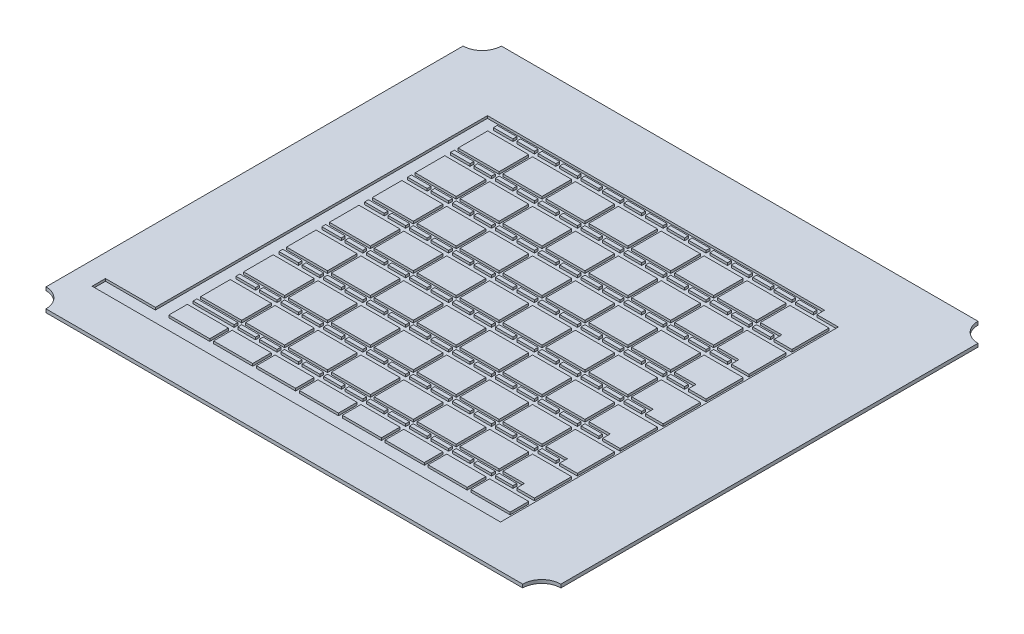
SolidWorks part; units mm, degrees
material "Acrylic (Medium-high impact)"
ref_plane "Front Plane" through (0, 0, 0) normal (0, 0, 1) x (1, 0, 0)
ref_plane "Top Plane" through (0, 0, 0) normal (0, 1, 0) x (1, 0, 0)
ref_plane "Right Plane" through (0, 0, 0) normal (1, 0, 0) x (0, 0, -1)
sketch "Sketch1" plane through (0, 0, 0) normal (0, 1, 0) x (1, 0, 0)
  line L1 (-342.9, -303.2125) -> (342.9, -303.2125)
  line L2 (-342.9, -303.2125) -> (-342.9, 303.2125)
  line L3 (-342.9, 303.2125) -> (342.9, 303.2125)
  line L4 (342.9, -303.2125) -> (342.9, 303.2125)
  line L5 (-342.9, -303.2125) -> (342.9, 303.2125) construction
  line L6 (-342.9, 303.2125) -> (342.9, -303.2125) construction
  point P0 (0, 0)
  dimension "D1" = 685.8
  dimension "D2" = 606.425
extrude "Boss-Extrude1" add sketch "Sketch1" along normal blind 4.4958
sketch "Sketch2" plane through (0, 4.4958, 0) normal (0, 1, 0) x (1, 0, 0)
  line L0 (0, 0) -> (0, 228.6) construction
  line L1 (0, 228.6) -> (228.6, 228.6) construction
  line L2 (228.6, 228.6) -> (228.6, -228.6) construction
  line L3 (228.6, -228.6) -> (-228.6, -228.6) construction
  line L4 (-228.6, -228.6) -> (-228.6, 228.6) construction
  line L5 (-228.6, 228.6) -> (0, 228.6) construction
  line L6 (0, 0) -> (0, -228.6) construction
  line L7 (-57.15, -228.6) -> (-57.15, 228.6) construction
  line L8 (-114.3, 228.6) -> (-114.3, -228.6) construction
  line L9 (-228.6, 0) -> (228.6, 0) construction
  line L10 (114.3, 228.6) -> (114.3, -228.6) construction
  line L11 (57.15, 228.6) -> (57.15, -228.6) construction
  line L12 (-228.6, 171.45) -> (228.6, 171.45) construction
  line L13 (-228.6, 114.3) -> (228.6, 114.3) construction
  line L14 (-228.6, 57.15) -> (228.6, 57.15) construction
  line L15 (228.6, -57.15) -> (-228.6, -57.15) construction
  line L16 (-228.6, -114.3) -> (228.6, -114.3) construction
  line L17 (228.6, -171.45) -> (-228.6, -171.45) construction
  line L18 (-171.45, 228.6) -> (-171.45, -228.6) construction
  line L19 (171.45, 228.6) -> (171.45, -228.6) construction
  dimension "D1" = 228.6
  dimension "D2" = 457.2
  dimension "D3" = 228.6
  dimension "D4" = 228.6
  dimension "D5" = 57.15
  dimension "D6" = 57.15
  dimension "D7" = 57.15
  dimension "D8" = 57.15
  dimension "D9" = 57.15
  dimension "D10" = 57.15
  dimension "D11" = 57.15
  dimension "D12" = 57.15
  dimension "D13" = 57.15
  dimension "D14" = 57.15
  dimension "D15" = 57.15
sketch "Sketch3" plane through (0, 4.4958, 0) normal (0, 1, 0) x (1, 0, 0)
  line L0 (0, 0) -> (0, -228.6) construction
  line L5 (-246.4078, -228.6) -> (-312.907, -228.6)
  line L6 (226.06, -228.6) -> (173.99, -228.6)
  line L7 (-228.6, -203.835) -> (-228.6, -228.6)
  line L8 (-228.6, 0) -> (228.6, 0) construction
  line L9 (-228.6, -191.135) -> (-228.6, -196.215)
  line L14 (231.14, -228.8655) -> (231.14, -246.38)
  line L15 (231.14, -246.38) -> (-312.907, -246.38)
  line L20 (-312.907, -228.6) -> (-312.907, -246.38)
  line L27 (-228.6, 208.915) -> (-228.6, 203.835)
  line L34 (-246.4078, 213.7295) -> (-246.4078, -228.6)
  line L39 (-228.6, -146.685) -> (-228.6, -186.055)
  line L40 (-228.6, -133.985) -> (-228.6, -139.065)
  line L43 (-228.6, -89.535) -> (-228.6, -128.905)
  line L45 (-228.6, -76.835) -> (-228.6, -81.915)
  line L46 (-228.6, -19.685) -> (-228.6, -24.765)
  line L51 (-228.6, -32.385) -> (-228.6, -71.755)
  line L52 (-228.6, 37.465) -> (-228.6, 32.385)
  line L57 (-228.6, 24.765) -> (-228.6, -14.605)
  line L58 (-228.6, 81.915) -> (-228.6, 42.545)
  line L68 (-228.6, 94.615) -> (-228.6, 89.535)
  line L71 (-228.6, 139.065) -> (-228.6, 99.695)
  line L73 (-228.6, 151.765) -> (-228.6, 146.685)
  line L74 (-228.6, 196.215) -> (-228.6, 156.845)
  line L90 (-173.99, -228.6) -> (-228.6, -228.6)
  line L94 (-116.84, -228.6) -> (-168.91, -228.6)
  line L127 (-59.69, -228.6) -> (-111.76, -228.6)
  line L130 (-2.54, -228.6) -> (-54.61, -228.6)
  line L159 (54.61, -228.6) -> (2.54, -228.6)
  line L162 (111.76, -228.6) -> (59.69, -228.6)
  line L166 (168.91, -228.6) -> (116.84, -228.6)
  line L171 (-168.91, 213.7295) -> (-246.4078, 213.7295)
  line L807 (202.565, -76.835) -> (202.565, -71.755)
  line L808 (226.06, -76.835) -> (226.06, -72.2386)
  line L809 (226.06, -133.985) -> (226.06, -128.905)
  line L810 (202.565, -133.985) -> (202.565, -128.905)
  line L811 (202.565, -191.135) -> (202.565, -186.055)
  line L812 (226.06, -191.135) -> (226.06, -186.055)
  line L813 (197.485, 32.385) -> (173.99, 32.385)
  line L814 (226.06, 37.465) -> (226.06, 42.545)
  line L815 (202.565, 37.465) -> (202.565, 42.545)
  line L816 (202.565, -19.685) -> (202.565, -14.605)
  line L817 (226.06, -19.685) -> (226.06, -14.605)
  line L818 (226.06, -71.755) -> (226.06, -72.2386)
  line L819 (197.485, -196.215) -> (173.99, -196.215)
  line L820 (197.485, 89.535) -> (173.99, 89.535)
  line L821 (197.485, 94.615) -> (173.99, 94.615)
  line L822 (197.485, 146.685) -> (173.99, 146.685)
  line L823 (197.485, 151.765) -> (173.99, 151.765)
  line L824 (83.185, 203.835) -> (59.69, 203.835)
  line L825 (83.185, 208.915) -> (59.69, 208.915)
  line L826 (140.335, 203.835) -> (116.84, 203.835)
  line L827 (140.335, 208.915) -> (116.84, 208.915)
  line L828 (197.485, 203.835) -> (173.99, 203.835)
  line L829 (197.485, 208.915) -> (173.99, 208.915)
  line L830 (140.335, 32.385) -> (116.84, 32.385)
  line L831 (140.335, 37.465) -> (116.84, 37.465)
  line L832 (140.335, 89.535) -> (116.84, 89.535)
  line L833 (140.335, 94.615) -> (116.84, 94.615)
  line L834 (140.335, 146.685) -> (116.84, 146.685)
  line L835 (140.335, 151.765) -> (116.84, 151.765)
  line L836 (83.185, 146.685) -> (59.69, 146.685)
  line L837 (83.185, 151.765) -> (59.69, 151.765)
  line L838 (83.185, 89.535) -> (59.69, 89.535)
  line L839 (83.185, 94.615) -> (59.69, 94.615)
  line L840 (83.185, 32.385) -> (59.69, 32.385)
  line L841 (83.185, 37.465) -> (59.69, 37.465)
  line L842 (26.035, 32.385) -> (2.54, 32.385)
  line L843 (26.035, 37.465) -> (2.54, 37.465)
  line L844 (26.035, 89.535) -> (2.54, 89.535)
  line L845 (26.035, 94.615) -> (2.54, 94.615)
  line L846 (26.035, 146.685) -> (2.54, 146.685)
  line L847 (26.035, 151.765) -> (2.54, 151.765)
  line L848 (26.035, 203.835) -> (2.54, 203.835)
  line L849 (26.035, 208.915) -> (2.54, 208.915)
  line L850 (-31.115, 32.385) -> (-54.61, 32.385)
  line L851 (-31.115, 37.465) -> (-54.61, 37.465)
  line L852 (-31.115, 89.535) -> (-54.61, 89.535)
  line L853 (-31.115, 94.615) -> (-54.61, 94.615)
  line L854 (-202.565, 89.535) -> (-228.6, 89.535)
  line L855 (-202.565, 94.615) -> (-228.6, 94.615)
  line L856 (-202.565, 32.385) -> (-228.6, 32.385)
  line L857 (-202.565, 37.465) -> (-228.6, 37.465)
  line L858 (-145.415, 37.465) -> (-168.91, 37.465)
  line L859 (-145.415, 32.385) -> (-168.91, 32.385)
  line L860 (-88.265, 32.385) -> (-111.76, 32.385)
  line L861 (-88.265, 37.465) -> (-111.76, 37.465)
  line L862 (-88.265, 89.535) -> (-111.76, 89.535)
  line L863 (-88.265, 94.615) -> (-111.76, 94.615)
  line L864 (-145.415, 89.535) -> (-168.91, 89.535)
  line L865 (-145.415, 94.615) -> (-168.91, 94.615)
  line L866 (-88.265, 146.685) -> (-111.76, 146.685)
  line L867 (-88.265, 151.765) -> (-111.76, 151.765)
  line L868 (-31.115, 146.685) -> (-54.61, 146.685)
  line L869 (-31.115, 151.765) -> (-54.61, 151.765)
  line L870 (-31.115, 203.835) -> (-54.61, 203.835)
  line L871 (-31.115, 208.915) -> (-54.61, 208.915)
  line L872 (-88.265, 203.835) -> (-111.76, 203.835)
  line L873 (-88.265, 208.915) -> (-111.76, 208.915)
  line L874 (-145.415, 203.835) -> (-168.91, 203.835)
  line L875 (-145.415, 208.915) -> (-168.91, 208.915)
  line L876 (-145.415, 146.685) -> (-168.91, 146.685)
  line L877 (-145.415, 151.765) -> (-168.91, 151.765)
  line L878 (-202.565, 146.685) -> (-228.6, 146.685)
  line L879 (-202.565, 151.765) -> (-228.6, 151.765)
  line L880 (-202.565, 203.835) -> (-228.6, 203.835)
  line L881 (-202.565, 208.915) -> (-228.6, 208.915)
  line L882 (197.485, -139.065) -> (173.99, -139.065)
  line L883 (197.485, -133.985) -> (173.99, -133.985)
  line L884 (197.485, -191.135) -> (173.99, -191.135)
  line L885 (140.335, -196.215) -> (116.84, -196.215)
  line L886 (140.335, -191.135) -> (116.84, -191.135)
  line L887 (140.335, -139.065) -> (116.84, -139.065)
  line L888 (140.335, -133.985) -> (116.84, -133.985)
  line L889 (83.185, -139.065) -> (59.69, -139.065)
  line L890 (83.185, -133.985) -> (59.69, -133.985)
  line L891 (83.185, -196.215) -> (59.69, -196.215)
  line L892 (83.185, -191.135) -> (59.69, -191.135)
  line L893 (26.035, -196.215) -> (2.54, -196.215)
  line L894 (26.035, -191.135) -> (2.54, -191.135)
  line L895 (26.035, -139.065) -> (2.54, -139.065)
  line L896 (26.035, -133.985) -> (2.54, -133.985)
  line L897 (-31.115, -139.065) -> (-54.61, -139.065)
  line L898 (-31.115, -133.985) -> (-54.61, -133.985)
  line L899 (-31.115, -196.215) -> (-54.61, -196.215)
  line L900 (-31.115, -191.135) -> (-54.61, -191.135)
  line L901 (-88.265, -196.215) -> (-111.76, -196.215)
  line L902 (-88.265, -191.135) -> (-111.76, -191.135)
  line L903 (-145.415, -196.215) -> (-168.91, -196.215)
  line L904 (-145.415, -191.135) -> (-168.91, -191.135)
  line L905 (-88.265, -139.065) -> (-111.76, -139.065)
  line L906 (-88.265, -133.985) -> (-111.76, -133.985)
  line L907 (-145.415, -139.065) -> (-168.91, -139.065)
  line L908 (-145.415, -133.985) -> (-168.91, -133.985)
  line L909 (-202.565, -139.065) -> (-228.6, -139.065)
  line L910 (-202.565, -133.985) -> (-228.6, -133.985)
  line L911 (-145.415, -81.915) -> (-168.91, -81.915)
  line L912 (-145.415, -76.835) -> (-168.91, -76.835)
  line L913 (-202.565, -81.915) -> (-228.6, -81.915)
  line L914 (-202.565, -76.835) -> (-228.6, -76.835)
  line L915 (-88.265, -81.915) -> (-111.76, -81.915)
  line L916 (-88.265, -76.835) -> (-111.76, -76.835)
  line L917 (-31.115, -81.915) -> (-54.61, -81.915)
  line L918 (-31.115, -76.835) -> (-54.61, -76.835)
  line L919 (26.035, -81.915) -> (2.54, -81.915)
  line L920 (26.035, -76.835) -> (2.54, -76.835)
  line L921 (83.185, -81.915) -> (59.69, -81.915)
  line L922 (83.185, -76.835) -> (59.69, -76.835)
  line L923 (140.335, -81.915) -> (116.84, -81.915)
  line L924 (140.335, -76.835) -> (116.84, -76.835)
  line L925 (197.485, -81.915) -> (173.99, -81.915)
  line L926 (197.485, -76.835) -> (173.99, -76.835)
  line L927 (197.485, -196.215) -> (197.485, -191.135)
  line L928 (202.565, -196.215) -> (202.565, -191.135)
  line L929 (140.335, -196.215) -> (140.335, -191.135)
  line L930 (145.415, -196.215) -> (145.415, -191.135)
  line L931 (83.185, -196.215) -> (83.185, -191.135)
  line L932 (88.265, -196.215) -> (88.265, -191.135)
  line L933 (26.035, -196.215) -> (26.035, -191.135)
  line L934 (31.115, -196.215) -> (31.115, -191.135)
  line L935 (-31.115, -196.215) -> (-31.115, -191.135)
  line L936 (-26.035, -196.215) -> (-26.035, -191.135)
  line L937 (-83.185, -196.215) -> (-83.185, -191.135)
  line L938 (-88.265, -196.215) -> (-88.265, -191.135)
  line L939 (-140.335, -196.215) -> (-140.335, -191.135)
  line L940 (-145.415, -196.215) -> (-145.415, -191.135)
  line L941 (-197.485, -196.215) -> (-197.485, -191.135)
  line L942 (-202.565, -196.215) -> (-202.565, -191.135)
  line L943 (197.485, -139.065) -> (197.485, -133.985)
  line L944 (202.565, -139.065) -> (202.565, -133.985)
  line L945 (140.335, -139.065) -> (140.335, -133.985)
  line L946 (145.415, -139.065) -> (145.415, -133.985)
  line L947 (83.185, -139.065) -> (83.185, -133.985)
  line L948 (88.265, -139.065) -> (88.265, -133.985)
  line L949 (26.035, -139.065) -> (26.035, -133.985)
  line L950 (31.115, -139.065) -> (31.115, -133.985)
  line L951 (-31.115, -139.065) -> (-31.115, -133.985)
  line L952 (-26.035, -139.065) -> (-26.035, -133.985)
  line L953 (-83.185, -139.065) -> (-83.185, -133.985)
  line L954 (-88.265, -139.065) -> (-88.265, -133.985)
  line L955 (-140.335, -139.065) -> (-140.335, -133.985)
  line L956 (-145.415, -139.065) -> (-145.415, -133.985)
  line L957 (-197.485, -139.065) -> (-197.485, -133.985)
  line L958 (-202.565, -139.065) -> (-202.565, -133.985)
  line L959 (197.485, -81.915) -> (197.485, -76.835)
  line L960 (202.565, -81.915) -> (202.565, -76.835)
  line L961 (140.335, -81.915) -> (140.335, -76.835)
  line L962 (145.415, -81.915) -> (145.415, -76.835)
  line L963 (83.185, -81.915) -> (83.185, -76.835)
  line L964 (88.265, -81.915) -> (88.265, -76.835)
  line L965 (26.035, -81.915) -> (26.035, -76.835)
  line L966 (31.115, -81.915) -> (31.115, -76.835)
  line L967 (-31.115, -81.915) -> (-31.115, -76.835)
  line L968 (-26.035, -81.915) -> (-26.035, -76.835)
  line L969 (-83.185, -81.915) -> (-83.185, -76.835)
  line L970 (-88.265, -81.915) -> (-88.265, -76.835)
  line L971 (-140.335, -81.915) -> (-140.335, -76.835)
  line L972 (-145.415, -81.915) -> (-145.415, -76.835)
  line L973 (-197.485, -81.915) -> (-197.485, -76.835)
  line L974 (-202.565, -81.915) -> (-202.565, -76.835)
  line L975 (197.485, 203.835) -> (197.485, 208.915)
  line L976 (202.565, 203.5695) -> (202.565, 208.6495)
  line L977 (140.335, 203.835) -> (140.335, 208.915)
  line L978 (145.415, 203.835) -> (145.415, 208.915)
  line L979 (83.185, 203.835) -> (83.185, 208.915)
  line L980 (88.265, 203.835) -> (88.265, 208.915)
  line L981 (26.035, 203.835) -> (26.035, 208.915)
  line L982 (31.115, 203.835) -> (31.115, 208.915)
  line L983 (-31.115, 203.835) -> (-31.115, 208.915)
  line L984 (-26.035, 203.835) -> (-26.035, 208.915)
  line L985 (-83.185, 203.835) -> (-83.185, 208.915)
  line L986 (-88.265, 203.835) -> (-88.265, 208.915)
  line L987 (-140.335, 203.835) -> (-140.335, 208.915)
  line L988 (-145.415, 203.835) -> (-145.415, 208.915)
  line L989 (-197.485, 203.835) -> (-197.485, 208.915)
  line L990 (-202.565, 203.835) -> (-202.565, 208.915)
  line L991 (197.485, 146.685) -> (197.485, 151.765)
  line L992 (202.565, 146.685) -> (202.565, 151.765)
  line L993 (140.335, 146.685) -> (140.335, 151.765)
  line L994 (145.415, 146.685) -> (145.415, 151.765)
  line L995 (83.185, 146.685) -> (83.185, 151.765)
  line L996 (88.265, 146.685) -> (88.265, 151.765)
  line L997 (26.035, 146.685) -> (26.035, 151.765)
  line L998 (31.115, 146.685) -> (31.115, 151.765)
  line L999 (-31.115, 146.685) -> (-31.115, 151.765)
  line L1000 (-26.035, 146.685) -> (-26.035, 151.765)
  line L1001 (-83.185, 146.685) -> (-83.185, 151.765)
  line L1002 (-88.265, 146.685) -> (-88.265, 151.765)
  line L1003 (-140.335, 146.685) -> (-140.335, 151.765)
  line L1004 (-145.415, 146.685) -> (-145.415, 151.765)
  line L1005 (-197.485, 146.685) -> (-197.485, 151.765)
  line L1006 (-202.565, 146.685) -> (-202.565, 151.765)
  line L1007 (197.485, 89.535) -> (197.485, 94.615)
  line L1008 (202.565, 89.535) -> (202.565, 94.615)
  line L1009 (140.335, 89.535) -> (140.335, 94.615)
  line L1010 (145.415, 89.535) -> (145.415, 94.615)
  line L1011 (83.185, 89.535) -> (83.185, 94.615)
  line L1012 (88.265, 89.535) -> (88.265, 94.615)
  line L1013 (26.035, 89.535) -> (26.035, 94.615)
  line L1014 (31.115, 89.535) -> (31.115, 94.615)
  line L1015 (-31.115, 89.535) -> (-31.115, 94.615)
  line L1016 (-26.035, 89.535) -> (-26.035, 94.615)
  line L1017 (-83.185, 89.535) -> (-83.185, 94.615)
  line L1018 (-88.265, 89.535) -> (-88.265, 94.615)
  line L1019 (-140.335, 89.535) -> (-140.335, 94.615)
  line L1020 (-145.415, 89.535) -> (-145.415, 94.615)
  line L1021 (-197.485, 89.535) -> (-197.485, 94.615)
  line L1022 (-202.565, 89.535) -> (-202.565, 94.615)
  line L1023 (197.485, 32.385) -> (197.485, 37.465)
  line L1024 (202.565, 32.385) -> (202.565, 37.465)
  line L1025 (140.335, 32.385) -> (140.335, 37.465)
  line L1026 (145.415, 32.385) -> (145.415, 37.465)
  line L1027 (83.185, 32.385) -> (83.185, 37.465)
  line L1028 (88.265, 32.385) -> (88.265, 37.465)
  line L1029 (26.035, 32.385) -> (26.035, 37.465)
  line L1030 (31.115, 32.385) -> (31.115, 37.465)
  line L1031 (-31.115, 32.385) -> (-31.115, 37.465)
  line L1032 (-26.035, 32.385) -> (-26.035, 37.465)
  line L1033 (-83.185, 32.385) -> (-83.185, 37.465)
  line L1034 (-88.265, 32.385) -> (-88.265, 37.465)
  line L1035 (-140.335, 32.385) -> (-140.335, 37.465)
  line L1036 (-145.415, 32.385) -> (-145.415, 37.465)
  line L1037 (-197.485, 32.385) -> (-197.485, 37.465)
  line L1038 (-202.565, 32.385) -> (-202.565, 37.465)
  line L1039 (-202.565, -24.765) -> (-228.6, -24.765)
  line L1040 (-202.565, -19.685) -> (-228.6, -19.685)
  line L1041 (-145.415, -24.765) -> (-168.91, -24.765)
  line L1042 (-145.415, -19.685) -> (-168.91, -19.685)
  line L1043 (-88.265, -24.765) -> (-111.76, -24.765)
  line L1044 (-88.265, -19.685) -> (-111.76, -19.685)
  line L1045 (-31.115, -24.765) -> (-54.61, -24.765)
  line L1046 (-31.115, -19.685) -> (-54.61, -19.685)
  line L1047 (26.035, -24.765) -> (2.54, -24.765)
  line L1048 (26.035, -19.685) -> (2.54, -19.685)
  line L1049 (83.185, -24.765) -> (59.69, -24.765)
  line L1050 (83.185, -19.685) -> (59.69, -19.685)
  line L1051 (140.335, -24.765) -> (116.84, -24.765)
  line L1052 (140.335, -19.685) -> (116.84, -19.685)
  line L1053 (197.485, -24.765) -> (173.99, -24.765)
  line L1054 (197.485, -19.685) -> (173.99, -19.685)
  line L1055 (-197.485, -24.765) -> (-197.485, -19.685)
  line L1056 (-202.565, -24.765) -> (-202.565, -19.685)
  line L1057 (-140.335, -24.765) -> (-140.335, -19.685)
  line L1058 (-145.415, -24.765) -> (-145.415, -19.685)
  line L1059 (-83.185, -24.765) -> (-83.185, -19.685)
  line L1060 (-88.265, -24.765) -> (-88.265, -19.685)
  line L1061 (-26.035, -24.765) -> (-26.035, -19.685)
  line L1062 (-31.115, -24.765) -> (-31.115, -19.685)
  line L1063 (31.115, -24.765) -> (31.115, -19.685)
  line L1064 (26.035, -24.765) -> (26.035, -19.685)
  line L1065 (88.265, -24.765) -> (88.265, -19.685)
  line L1066 (83.185, -24.765) -> (83.185, -19.685)
  line L1067 (145.415, -24.765) -> (145.415, -19.685)
  line L1068 (140.335, -24.765) -> (140.335, -19.685)
  line L1069 (197.485, -24.765) -> (197.485, -19.685)
  line L1070 (202.565, -24.765) -> (202.565, -19.685)
  line L1071 (-173.99, -191.135) -> (-173.99, -196.215)
  line L1072 (-168.91, -191.135) -> (-168.91, -196.215)
  line L1073 (-173.99, -203.835) -> (-173.99, -228.6)
  line L1074 (-168.91, -203.835) -> (-168.91, -228.6)
  line L1075 (-116.84, -191.135) -> (-116.84, -196.215)
  line L1076 (-111.76, -191.135) -> (-111.76, -196.215)
  line L1077 (-116.84, -203.835) -> (-116.84, -228.6)
  line L1078 (-111.76, -203.835) -> (-111.76, -228.6)
  line L1079 (-59.69, -203.835) -> (-59.69, -228.6)
  line L1080 (-54.61, -203.835) -> (-54.61, -228.6)
  line L1081 (-59.69, -191.135) -> (-59.69, -196.215)
  line L1082 (-54.61, -191.135) -> (-54.61, -196.215)
  line L1083 (-2.54, -191.135) -> (-2.54, -196.215)
  line L1084 (2.54, -191.135) -> (2.54, -196.215)
  line L1085 (-2.54, -203.835) -> (-2.54, -228.6)
  line L1086 (2.54, -203.835) -> (2.54, -228.6)
  line L1087 (54.61, -203.835) -> (54.61, -228.6)
  line L1088 (59.69, -203.835) -> (59.69, -228.6)
  line L1089 (54.61, -191.135) -> (54.61, -196.215)
  line L1090 (59.69, -191.135) -> (59.69, -196.215)
  line L1091 (111.76, -191.135) -> (111.76, -196.215)
  line L1092 (116.84, -191.135) -> (116.84, -196.215)
  line L1093 (111.76, -203.835) -> (111.76, -228.6)
  line L1094 (116.84, -203.835) -> (116.84, -228.6)
  line L1095 (168.91, -203.835) -> (168.91, -228.6)
  line L1096 (173.99, -203.835) -> (173.99, -228.6)
  line L1097 (168.91, -191.135) -> (168.91, -196.215)
  line L1098 (173.99, -191.135) -> (173.99, -196.215)
  line L1099 (226.06, -191.135) -> (226.06, -196.215)
  line L1100 (226.06, -203.835) -> (226.06, -228.6)
  line L1101 (226.06, -133.985) -> (226.06, -139.065)
  line L1102 (226.06, -146.685) -> (226.06, -186.055)
  line L1103 (168.91, -133.985) -> (168.91, -139.065)
  line L1104 (173.99, -133.985) -> (173.99, -139.065)
  line L1105 (168.91, -146.685) -> (168.91, -186.055)
  line L1106 (173.99, -146.685) -> (173.99, -186.055)
  line L1107 (111.76, -146.685) -> (111.76, -186.055)
  line L1108 (116.84, -146.685) -> (116.84, -186.055)
  line L1109 (111.76, -133.985) -> (111.76, -139.065)
  line L1110 (116.84, -133.985) -> (116.84, -139.065)
  line L1111 (54.61, -146.685) -> (54.61, -186.055)
  line L1112 (59.69, -146.685) -> (59.69, -186.055)
  line L1113 (54.61, -133.985) -> (54.61, -139.065)
  line L1114 (59.69, -133.985) -> (59.69, -139.065)
  line L1115 (2.54, -146.685) -> (2.54, -186.055)
  line L1116 (-2.54, -146.685) -> (-2.54, -186.055)
  line L1117 (-2.54, -133.985) -> (-2.54, -139.065)
  line L1118 (2.54, -133.985) -> (2.54, -139.065)
  line L1119 (-59.69, -146.685) -> (-59.69, -186.055)
  line L1120 (-54.61, -146.685) -> (-54.61, -186.055)
  line L1121 (-54.61, -133.985) -> (-54.61, -139.065)
  line L1122 (-59.69, -133.985) -> (-59.69, -139.065)
  line L1123 (-116.84, -133.985) -> (-116.84, -139.065)
  line L1124 (-111.76, -133.985) -> (-111.76, -139.065)
  line L1125 (-111.76, -146.685) -> (-111.76, -186.055)
  line L1126 (-116.84, -146.685) -> (-116.84, -186.055)
  line L1127 (-173.99, -146.685) -> (-173.99, -186.055)
  line L1128 (-168.91, -146.685) -> (-168.91, -186.055)
  line L1129 (-168.91, -133.985) -> (-168.91, -139.065)
  line L1130 (-173.99, -133.985) -> (-173.99, -139.065)
  line L1131 (-173.99, -89.535) -> (-173.99, -128.905)
  line L1132 (-168.91, -89.535) -> (-168.91, -128.905)
  line L1133 (-173.99, -76.835) -> (-173.99, -81.915)
  line L1134 (-168.91, -76.835) -> (-168.91, -81.915)
  line L1135 (-116.84, -76.835) -> (-116.84, -81.915)
  line L1136 (-111.76, -76.835) -> (-111.76, -81.915)
  line L1137 (-116.84, -89.535) -> (-116.84, -128.905)
  line L1138 (-111.76, -89.535) -> (-111.76, -128.905)
  line L1139 (-59.69, -76.835) -> (-59.69, -81.915)
  line L1140 (-54.61, -76.835) -> (-54.61, -81.915)
  line L1141 (-59.69, -89.535) -> (-59.69, -128.905)
  line L1142 (-54.61, -89.535) -> (-54.61, -128.905)
  line L1143 (-2.54, -76.835) -> (-2.54, -81.915)
  line L1144 (2.54, -76.835) -> (2.54, -81.915)
  line L1145 (-2.54, -89.535) -> (-2.54, -128.905)
  line L1146 (2.54, -89.535) -> (2.54, -128.905)
  line L1147 (54.61, -89.535) -> (54.61, -128.905)
  line L1148 (59.69, -89.535) -> (59.69, -128.905)
  line L1149 (54.61, -76.835) -> (54.61, -81.915)
  line L1150 (59.69, -76.835) -> (59.69, -81.915)
  line L1151 (111.76, -76.835) -> (111.76, -81.915)
  line L1152 (116.84, -76.835) -> (116.84, -81.915)
  line L1153 (111.76, -89.535) -> (111.76, -128.905)
  line L1154 (116.84, -89.535) -> (116.84, -128.905)
  line L1155 (168.91, -89.535) -> (168.91, -128.905)
  line L1156 (173.99, -89.535) -> (173.99, -128.905)
  line L1157 (226.06, -89.535) -> (226.06, -128.905)
  line L1158 (168.91, -76.835) -> (168.91, -81.915)
  line L1159 (173.99, -76.835) -> (173.99, -81.915)
  line L1160 (226.06, -76.835) -> (226.06, -81.915)
  line L1161 (-173.99, 37.465) -> (-173.99, 32.385)
  line L1162 (-168.91, 37.465) -> (-168.91, 32.385)
  line L1163 (-173.99, 24.765) -> (-173.99, -14.605)
  line L1164 (-168.91, 24.765) -> (-168.91, -14.605)
  line L1165 (-116.84, 24.765) -> (-116.84, -14.605)
  line L1166 (-111.76, 24.765) -> (-111.76, -14.605)
  line L1167 (-116.84, 37.465) -> (-116.84, 32.385)
  line L1168 (-111.76, 37.465) -> (-111.76, 32.385)
  line L1169 (-59.69, 37.465) -> (-59.69, 32.385)
  line L1170 (-54.61, 37.465) -> (-54.61, 32.385)
  line L1171 (-59.69, 24.765) -> (-59.69, -14.605)
  line L1172 (-54.61, 24.765) -> (-54.61, -14.605)
  line L1173 (-2.54, 37.465) -> (-2.54, 32.385)
  line L1174 (2.54, 37.465) -> (2.54, 32.385)
  line L1175 (-2.54, 24.765) -> (-2.54, -14.605)
  line L1176 (2.54, 24.765) -> (2.54, -14.605)
  line L1177 (54.61, 24.765) -> (54.61, -14.605)
  line L1178 (59.69, 24.765) -> (59.69, -14.605)
  line L1179 (54.61, 37.465) -> (54.61, 32.385)
  line L1180 (59.69, 37.465) -> (59.69, 32.385)
  line L1181 (111.76, 24.765) -> (111.76, -14.605)
  line L1182 (116.84, 24.765) -> (116.84, -14.605)
  line L1183 (111.76, 37.465) -> (111.76, 32.385)
  line L1184 (116.84, 37.465) -> (116.84, 32.385)
  line L1185 (168.91, 37.465) -> (168.91, 32.385)
  line L1186 (173.99, 37.465) -> (173.99, 32.385)
  line L1187 (226.06, 37.465) -> (226.06, 32.385)
  line L1188 (168.91, 24.765) -> (168.91, -14.605)
  line L1189 (173.99, 24.765) -> (173.99, -14.605)
  line L1190 (226.06, 24.765) -> (226.06, -14.605)
  line L1191 (-173.99, 94.615) -> (-173.99, 89.535)
  line L1192 (-168.91, 94.615) -> (-168.91, 89.535)
  line L1193 (-173.99, 81.915) -> (-173.99, 42.545)
  line L1194 (-168.91, 81.915) -> (-168.91, 42.545)
  line L1195 (-116.84, 94.615) -> (-116.84, 89.535)
  line L1196 (-111.76, 94.615) -> (-111.76, 89.535)
  line L1197 (-116.84, 81.915) -> (-116.84, 42.545)
  line L1198 (-111.76, 81.915) -> (-111.76, 42.545)
  line L1199 (-59.69, 81.915) -> (-59.69, 42.545)
  line L1200 (-54.61, 81.915) -> (-54.61, 42.545)
  line L1201 (-59.69, 94.615) -> (-59.69, 89.535)
  line L1202 (-54.61, 94.615) -> (-54.61, 89.535)
  line L1203 (-2.54, 94.615) -> (-2.54, 89.535)
  line L1204 (2.54, 94.615) -> (2.54, 89.535)
  line L1205 (-2.54, 81.915) -> (-2.54, 42.545)
  line L1206 (2.54, 81.915) -> (2.54, 42.545)
  line L1207 (54.61, 81.915) -> (54.61, 42.545)
  line L1208 (59.69, 81.915) -> (59.69, 42.545)
  line L1209 (54.61, 94.615) -> (54.61, 89.535)
  line L1210 (59.69, 94.615) -> (59.69, 89.535)
  line L1211 (111.76, 94.615) -> (111.76, 89.535)
  line L1212 (116.84, 94.615) -> (116.84, 89.535)
  line L1213 (111.76, 81.915) -> (111.76, 42.545)
  line L1214 (116.84, 81.915) -> (116.84, 42.545)
  line L1215 (168.91, 81.915) -> (168.91, 42.545)
  line L1216 (173.99, 81.915) -> (173.99, 42.545)
  line L1217 (226.06, 81.915) -> (226.06, 42.545)
  line L1218 (168.91, 94.615) -> (168.91, 89.535)
  line L1219 (173.99, 94.615) -> (173.99, 89.535)
  line L1220 (226.06, 94.615) -> (226.06, 89.535)
  line L1221 (226.06, 139.065) -> (226.06, 99.695)
  line L1222 (226.06, 151.765) -> (226.06, 146.685)
  line L1223 (168.91, 151.765) -> (168.91, 146.685)
  line L1224 (173.99, 151.765) -> (173.99, 146.685)
  line L1225 (168.91, 139.065) -> (168.91, 99.695)
  line L1226 (173.99, 139.065) -> (173.99, 99.695)
  line L1227 (111.76, 139.065) -> (111.76, 99.695)
  line L1228 (116.84, 139.065) -> (116.84, 99.695)
  line L1229 (111.76, 151.765) -> (111.76, 146.685)
  line L1230 (116.84, 151.765) -> (116.84, 146.685)
  line L1231 (54.61, 139.065) -> (54.61, 99.695)
  line L1232 (59.69, 139.065) -> (59.69, 99.695)
  line L1233 (54.61, 151.765) -> (54.61, 146.685)
  line L1234 (59.69, 151.765) -> (59.69, 146.685)
  line L1235 (-2.54, 151.765) -> (-2.54, 146.685)
  line L1236 (2.54, 151.765) -> (2.54, 146.685)
  line L1237 (-2.54, 139.065) -> (-2.54, 99.695)
  line L1238 (2.54, 139.065) -> (2.54, 99.695)
  line L1239 (-59.69, 139.065) -> (-59.69, 99.695)
  line L1240 (-54.61, 139.065) -> (-54.61, 99.695)
  line L1241 (-59.69, 151.765) -> (-59.69, 146.685)
  line L1242 (-54.61, 151.765) -> (-54.61, 146.685)
  line L1243 (-116.84, 151.765) -> (-116.84, 146.685)
  line L1244 (-111.76, 151.765) -> (-111.76, 146.685)
  line L1245 (-116.84, 139.065) -> (-116.84, 99.695)
  line L1246 (-111.76, 139.065) -> (-111.76, 99.695)
  line L1247 (-173.99, 139.065) -> (-173.99, 99.695)
  line L1248 (-168.91, 139.065) -> (-168.91, 99.695)
  line L1249 (-173.99, 151.765) -> (-173.99, 146.685)
  line L1250 (-168.91, 151.765) -> (-168.91, 146.685)
  line L1251 (-173.99, 208.915) -> (-173.99, 203.835)
  line L1252 (-168.91, 208.915) -> (-168.91, 203.835)
  line L1253 (-173.99, 196.215) -> (-173.99, 156.845)
  line L1254 (-168.91, 196.215) -> (-168.91, 156.845)
  line L1255 (-116.84, 196.215) -> (-116.84, 156.845)
  line L1256 (-111.76, 196.215) -> (-111.76, 156.845)
  line L1257 (-116.84, 208.915) -> (-116.84, 203.835)
  line L1258 (-111.76, 208.915) -> (-111.76, 203.835)
  line L1259 (-59.69, 196.215) -> (-59.69, 156.845)
  line L1260 (-54.61, 196.215) -> (-54.61, 156.845)
  line L1261 (-59.69, 208.915) -> (-59.69, 203.835)
  line L1262 (-54.61, 208.915) -> (-54.61, 203.835)
  line L1263 (-2.54, 208.915) -> (-2.54, 203.835)
  line L1264 (2.54, 208.915) -> (2.54, 203.835)
  line L1265 (-2.54, 196.215) -> (-2.54, 156.845)
  line L1266 (2.54, 196.215) -> (2.54, 156.845)
  line L1267 (54.61, 196.215) -> (54.61, 156.845)
  line L1268 (59.69, 196.215) -> (59.69, 156.845)
  line L1269 (54.61, 208.915) -> (54.61, 203.835)
  line L1270 (59.69, 208.915) -> (59.69, 203.835)
  line L1271 (111.76, 196.215) -> (111.76, 156.845)
  line L1272 (116.84, 196.215) -> (116.84, 156.845)
  line L1273 (111.76, 208.915) -> (111.76, 203.835)
  line L1274 (116.84, 208.915) -> (116.84, 203.835)
  line L1275 (168.91, 208.915) -> (168.91, 203.835)
  line L1276 (173.99, 208.915) -> (173.99, 203.835)
  line L1277 (168.91, 196.215) -> (168.91, 156.845)
  line L1278 (173.99, 196.215) -> (173.99, 156.845)
  line L1279 (226.06, 196.215) -> (226.06, 156.845)
  line L1281 (-173.99, 208.915) -> (-197.485, 208.915)
  line L1282 (-173.99, 203.835) -> (-197.485, 203.835)
  line L1283 (-173.99, 196.215) -> (-228.6, 196.215)
  line L1284 (-116.84, 196.215) -> (-168.91, 196.215)
  line L1285 (-116.84, 203.835) -> (-140.335, 203.835)
  line L1286 (-116.84, 208.915) -> (-140.335, 208.915)
  line L1287 (-116.84, 213.7295) -> (-168.91, 213.7295)
  line L1288 (-59.69, 213.7295) -> (-111.76, 213.7295)
  line L1289 (-59.69, 208.915) -> (-83.185, 208.915)
  line L1290 (-59.69, 203.835) -> (-83.185, 203.835)
  line L1291 (-59.69, 196.215) -> (-111.76, 196.215)
  line L1292 (-2.54, 213.7295) -> (-54.61, 213.7295)
  line L1293 (-2.54, 208.915) -> (-26.035, 208.915)
  line L1294 (-2.54, 203.835) -> (-26.035, 203.835)
  line L1295 (-2.54, 196.215) -> (-54.61, 196.215)
  line L1296 (54.61, 213.7295) -> (2.54, 213.7295)
  line L1297 (54.61, 208.915) -> (31.115, 208.915)
  line L1298 (54.61, 203.835) -> (31.115, 203.835)
  line L1299 (54.61, 196.215) -> (2.54, 196.215)
  line L1300 (111.76, 213.7295) -> (59.69, 213.7295)
  line L1301 (111.76, 208.915) -> (88.265, 208.915)
  line L1302 (111.76, 203.835) -> (88.265, 203.835)
  line L1303 (111.76, 196.215) -> (59.69, 196.215)
  line L1304 (168.91, 213.7295) -> (116.84, 213.7295)
  line L1305 (168.91, 208.915) -> (145.415, 208.915)
  line L1306 (168.91, 203.835) -> (145.415, 203.835)
  line L1307 (168.91, 196.215) -> (116.84, 196.215)
  line L1308 (226.06, 196.215) -> (173.99, 196.215)
  line L1309 (226.06, 203.5695) -> (202.565, 203.5695)
  line L1310 (202.565, 213.7295) -> (173.99, 213.7295)
  line L1311 (-173.99, 156.845) -> (-228.6, 156.845)
  line L1312 (-173.99, 151.765) -> (-197.485, 151.765)
  line L1313 (-173.99, 146.685) -> (-197.485, 146.685)
  line L1314 (-173.99, 139.065) -> (-228.6, 139.065)
  line L1315 (-116.84, 139.065) -> (-168.91, 139.065)
  line L1316 (-116.84, 146.685) -> (-140.335, 146.685)
  line L1317 (-116.84, 151.765) -> (-140.335, 151.765)
  line L1318 (-116.84, 156.845) -> (-168.91, 156.845)
  line L1319 (-59.69, 156.845) -> (-111.76, 156.845)
  line L1320 (-59.69, 151.765) -> (-83.185, 151.765)
  line L1321 (-59.69, 146.685) -> (-83.185, 146.685)
  line L1322 (-59.69, 139.065) -> (-111.76, 139.065)
  line L1323 (-2.54, 156.845) -> (-54.61, 156.845)
  line L1324 (-2.54, 151.765) -> (-26.035, 151.765)
  line L1325 (-2.54, 146.685) -> (-26.035, 146.685)
  line L1326 (-2.54, 139.065) -> (-54.61, 139.065)
  line L1327 (54.61, 156.845) -> (2.54, 156.845)
  line L1328 (54.61, 151.765) -> (31.115, 151.765)
  line L1329 (54.61, 146.685) -> (31.115, 146.685)
  line L1330 (54.61, 139.065) -> (2.54, 139.065)
  line L1331 (111.76, 156.845) -> (59.69, 156.845)
  line L1332 (111.76, 151.765) -> (88.265, 151.765)
  line L1333 (111.76, 146.685) -> (88.265, 146.685)
  line L1334 (111.76, 139.065) -> (59.69, 139.065)
  line L1335 (168.91, 156.845) -> (116.84, 156.845)
  line L1336 (168.91, 151.765) -> (145.415, 151.765)
  line L1337 (168.91, 146.685) -> (145.415, 146.685)
  line L1338 (168.91, 139.065) -> (116.84, 139.065)
  line L1339 (226.06, 139.065) -> (173.99, 139.065)
  line L1340 (226.06, 146.685) -> (202.565, 146.685)
  line L1341 (202.565, 156.845) -> (173.99, 156.845)
  line L1342 (-173.99, 99.695) -> (-228.6, 99.695)
  line L1343 (-173.99, 94.615) -> (-197.485, 94.615)
  line L1344 (-173.99, 89.535) -> (-197.485, 89.535)
  line L1345 (-173.99, 81.915) -> (-228.6, 81.915)
  line L1346 (-116.84, 81.915) -> (-168.91, 81.915)
  line L1347 (-116.84, 89.535) -> (-140.335, 89.535)
  line L1348 (-116.84, 94.615) -> (-140.335, 94.615)
  line L1349 (-116.84, 99.695) -> (-168.91, 99.695)
  line L1350 (-59.69, 99.695) -> (-111.76, 99.695)
  line L1351 (-59.69, 94.615) -> (-83.185, 94.615)
  line L1352 (-59.69, 89.535) -> (-83.185, 89.535)
  line L1353 (-59.69, 81.915) -> (-111.76, 81.915)
  line L1354 (-2.54, 99.695) -> (-54.61, 99.695)
  line L1355 (-2.54, 94.615) -> (-26.035, 94.615)
  line L1356 (-2.54, 89.535) -> (-26.035, 89.535)
  line L1357 (-2.54, 81.915) -> (-54.61, 81.915)
  line L1358 (54.61, 99.695) -> (2.54, 99.695)
  line L1359 (54.61, 94.615) -> (31.115, 94.615)
  line L1360 (54.61, 89.535) -> (31.115, 89.535)
  line L1361 (54.61, 81.915) -> (2.54, 81.915)
  line L1362 (111.76, 99.695) -> (59.69, 99.695)
  line L1363 (111.76, 94.615) -> (88.265, 94.615)
  line L1364 (111.76, 89.535) -> (88.265, 89.535)
  line L1365 (111.76, 81.915) -> (59.69, 81.915)
  line L1366 (168.91, 99.695) -> (116.84, 99.695)
  line L1367 (168.91, 94.615) -> (145.415, 94.615)
  line L1368 (168.91, 89.535) -> (145.415, 89.535)
  line L1369 (168.91, 81.915) -> (116.84, 81.915)
  line L1370 (226.06, 81.915) -> (173.99, 81.915)
  line L1371 (226.06, 89.535) -> (202.565, 89.535)
  line L1372 (202.565, 99.695) -> (173.99, 99.695)
  line L1373 (-173.99, 42.545) -> (-228.6, 42.545)
  line L1374 (-173.99, 37.465) -> (-197.485, 37.465)
  line L1375 (-173.99, 32.385) -> (-197.485, 32.385)
  line L1376 (-173.99, 24.765) -> (-228.6, 24.765)
  line L1377 (-116.84, 24.765) -> (-168.91, 24.765)
  line L1378 (-116.84, 32.385) -> (-140.335, 32.385)
  line L1379 (-116.84, 37.465) -> (-140.335, 37.465)
  line L1380 (-116.84, 42.545) -> (-168.91, 42.545)
  line L1381 (-59.69, 42.545) -> (-111.76, 42.545)
  line L1382 (-59.69, 37.465) -> (-83.185, 37.465)
  line L1383 (-59.69, 32.385) -> (-83.185, 32.385)
  line L1384 (-59.69, 24.765) -> (-111.76, 24.765)
  line L1385 (-2.54, 42.545) -> (-54.61, 42.545)
  line L1386 (-2.54, 37.465) -> (-26.035, 37.465)
  line L1387 (-2.54, 32.385) -> (-26.035, 32.385)
  line L1388 (-2.54, 24.765) -> (-54.61, 24.765)
  line L1389 (54.61, 42.545) -> (2.54, 42.545)
  line L1390 (54.61, 37.465) -> (31.115, 37.465)
  line L1391 (54.61, 32.385) -> (31.115, 32.385)
  line L1392 (54.61, 24.765) -> (2.54, 24.765)
  line L1393 (111.76, 42.545) -> (59.69, 42.545)
  line L1394 (111.76, 37.465) -> (88.265, 37.465)
  line L1395 (111.76, 32.385) -> (88.265, 32.385)
  line L1396 (111.76, 24.765) -> (59.69, 24.765)
  line L1397 (168.91, 42.545) -> (116.84, 42.545)
  line L1398 (168.91, 37.465) -> (145.415, 37.465)
  line L1399 (168.91, 32.385) -> (145.415, 32.385)
  line L1400 (168.91, 24.765) -> (116.84, 24.765)
  line L1401 (226.06, 24.765) -> (173.99, 24.765)
  line L1402 (226.06, 32.385) -> (202.565, 32.385)
  line L1403 (197.485, 37.465) -> (173.99, 37.465)
  line L1404 (202.565, 42.545) -> (173.99, 42.545)
  line L1405 (-173.99, -186.055) -> (-228.6, -186.055)
  line L1406 (-173.99, -191.135) -> (-228.6, -191.135)
  line L1407 (-173.99, -196.215) -> (-228.6, -196.215)
  line L1408 (-173.99, -203.835) -> (-228.6, -203.835)
  line L1409 (-116.84, -203.835) -> (-168.91, -203.835)
  line L1410 (-116.84, -196.215) -> (-140.335, -196.215)
  line L1411 (-116.84, -191.135) -> (-140.335, -191.135)
  line L1412 (-116.84, -186.055) -> (-168.91, -186.055)
  line L1413 (-59.69, -186.055) -> (-111.76, -186.055)
  line L1414 (-59.69, -191.135) -> (-83.185, -191.135)
  line L1415 (-59.69, -196.215) -> (-83.185, -196.215)
  line L1416 (-59.69, -203.835) -> (-111.76, -203.835)
  line L1417 (-2.54, -186.055) -> (-54.61, -186.055)
  line L1418 (-2.54, -191.135) -> (-26.035, -191.135)
  line L1419 (-2.54, -196.215) -> (-26.035, -196.215)
  line L1420 (-2.54, -203.835) -> (-54.61, -203.835)
  line L1421 (54.61, -186.055) -> (2.54, -186.055)
  line L1422 (54.61, -191.135) -> (31.115, -191.135)
  line L1423 (54.61, -196.215) -> (31.115, -196.215)
  line L1424 (54.61, -203.835) -> (2.54, -203.835)
  line L1425 (111.76, -186.055) -> (59.69, -186.055)
  line L1426 (111.76, -191.135) -> (88.265, -191.135)
  line L1427 (111.76, -196.215) -> (88.265, -196.215)
  line L1428 (111.76, -203.835) -> (59.69, -203.835)
  line L1429 (168.91, -186.055) -> (116.84, -186.055)
  line L1430 (168.91, -191.135) -> (145.415, -191.135)
  line L1431 (168.91, -196.215) -> (145.415, -196.215)
  line L1432 (168.91, -203.835) -> (116.84, -203.835)
  line L1433 (226.06, -203.835) -> (173.99, -203.835)
  line L1434 (226.06, -196.215) -> (202.565, -196.215)
  line L1436 (202.565, -186.055) -> (173.99, -186.055)
  line L1437 (-173.99, -128.905) -> (-228.6, -128.905)
  line L1438 (-173.99, -133.985) -> (-197.485, -133.985)
  line L1439 (-173.99, -139.065) -> (-197.485, -139.065)
  line L1440 (-173.99, -146.685) -> (-228.6, -146.685)
  line L1441 (-116.84, -146.685) -> (-168.91, -146.685)
  line L1442 (-116.84, -139.065) -> (-140.335, -139.065)
  line L1443 (-116.84, -133.985) -> (-140.335, -133.985)
  line L1444 (-116.84, -128.905) -> (-168.91, -128.905)
  line L1445 (-59.69, -128.905) -> (-111.76, -128.905)
  line L1446 (-59.69, -133.985) -> (-83.185, -133.985)
  line L1447 (-59.69, -139.065) -> (-83.185, -139.065)
  line L1448 (-59.69, -146.685) -> (-111.76, -146.685)
  line L1449 (-2.54, -128.905) -> (-54.61, -128.905)
  line L1450 (-2.54, -133.985) -> (-26.035, -133.985)
  line L1451 (-2.54, -139.065) -> (-26.035, -139.065)
  line L1452 (-2.54, -146.685) -> (-54.61, -146.685)
  line L1453 (54.61, -128.905) -> (2.54, -128.905)
  line L1454 (54.61, -133.985) -> (31.115, -133.985)
  line L1455 (54.61, -139.065) -> (31.115, -139.065)
  line L1456 (54.61, -146.685) -> (2.54, -146.685)
  line L1457 (111.76, -128.905) -> (59.69, -128.905)
  line L1458 (111.76, -133.985) -> (88.265, -133.985)
  line L1459 (111.76, -139.065) -> (88.265, -139.065)
  line L1460 (111.76, -146.685) -> (59.69, -146.685)
  line L1461 (168.91, -128.905) -> (116.84, -128.905)
  line L1462 (168.91, -133.985) -> (145.415, -133.985)
  line L1463 (168.91, -139.065) -> (145.415, -139.065)
  line L1464 (168.91, -146.685) -> (116.84, -146.685)
  line L1465 (226.06, -146.685) -> (173.99, -146.685)
  line L1466 (226.06, -139.065) -> (202.565, -139.065)
  line L1467 (202.565, -128.905) -> (173.99, -128.905)
  line L1468 (-173.99, -71.755) -> (-228.6, -71.755)
  line L1469 (-173.99, -76.835) -> (-197.485, -76.835)
  line L1470 (-173.99, -81.915) -> (-197.485, -81.915)
  line L1471 (-173.99, -89.535) -> (-228.6, -89.535)
  line L1472 (-116.84, -89.535) -> (-168.91, -89.535)
  line L1473 (-116.84, -81.915) -> (-140.335, -81.915)
  line L1474 (-116.84, -76.835) -> (-140.335, -76.835)
  line L1475 (-116.84, -71.755) -> (-168.91, -71.755)
  line L1476 (-59.69, -71.755) -> (-111.76, -71.755)
  line L1477 (-59.69, -76.835) -> (-83.185, -76.835)
  line L1478 (-59.69, -81.915) -> (-83.185, -81.915)
  line L1479 (-59.69, -89.535) -> (-111.76, -89.535)
  line L1480 (-2.54, -71.755) -> (-54.61, -71.755)
  line L1481 (-2.54, -76.835) -> (-26.035, -76.835)
  line L1482 (-2.54, -81.915) -> (-26.035, -81.915)
  line L1483 (-2.54, -89.535) -> (-54.61, -89.535)
  line L1484 (54.61, -71.755) -> (2.54, -71.755)
  line L1485 (54.61, -76.835) -> (31.115, -76.835)
  line L1486 (54.61, -81.915) -> (31.115, -81.915)
  line L1487 (54.61, -89.535) -> (2.54, -89.535)
  line L1488 (111.76, -71.755) -> (59.69, -71.755)
  line L1489 (111.76, -76.835) -> (88.265, -76.835)
  line L1490 (111.76, -81.915) -> (88.265, -81.915)
  line L1491 (111.76, -89.535) -> (59.69, -89.535)
  line L1492 (168.91, -71.755) -> (116.84, -71.755)
  line L1493 (168.91, -76.835) -> (145.415, -76.835)
  line L1494 (168.91, -81.915) -> (145.415, -81.915)
  line L1495 (168.91, -89.535) -> (116.84, -89.535)
  line L1496 (226.06, -89.535) -> (173.99, -89.535)
  line L1497 (226.06, -81.915) -> (202.565, -81.915)
  line L1498 (202.565, -71.755) -> (173.99, -71.755)
  line L1499 (-116.84, -14.605) -> (-168.91, -14.605)
  line L1500 (168.91, -14.605) -> (116.84, -14.605)
  line L1501 (-173.99, -19.685) -> (-197.485, -19.685)
  line L1502 (-173.99, -24.765) -> (-197.485, -24.765)
  line L1503 (-173.99, -32.385) -> (-228.6, -32.385)
  line L1504 (-116.84, -32.385) -> (-168.91, -32.385)
  line L1505 (-116.84, -24.765) -> (-140.335, -24.765)
  line L1506 (-116.84, -19.685) -> (-140.335, -19.685)
  line L1507 (-173.99, -14.605) -> (-228.6, -14.605)
  line L1508 (-59.69, -32.385) -> (-111.76, -32.385)
  line L1509 (-59.69, -14.605) -> (-111.76, -14.605)
  line L1510 (-59.69, -24.765) -> (-83.185, -24.765)
  line L1511 (-59.69, -19.685) -> (-83.185, -19.685)
  line L1512 (111.76, -14.605) -> (59.69, -14.605)
  line L1513 (54.61, -14.605) -> (2.54, -14.605)
  line L1514 (54.61, -19.685) -> (31.115, -19.685)
  line L1515 (54.61, -24.765) -> (31.115, -24.765)
  line L1516 (54.61, -32.385) -> (2.54, -32.385)
  line L1517 (111.76, -32.385) -> (59.69, -32.385)
  line L1518 (111.76, -24.765) -> (88.265, -24.765)
  line L1519 (111.76, -19.685) -> (88.265, -19.685)
  line L1520 (168.91, -32.385) -> (116.84, -32.385)
  line L1521 (168.91, -24.765) -> (145.415, -24.765)
  line L1522 (168.91, -19.685) -> (145.415, -19.685)
  line L1523 (231.14, -19.9505) -> (231.14, -14.8705)
  line L1524 (231.14, -32.6505) -> (231.14, -25.0305)
  line L1525 (226.06, -19.685) -> (226.06, -24.765)
  line L1526 (231.14, -19.9505) -> (231.14, -25.0305)
  line L1527 (202.565, 94.615) -> (202.565, 99.695)
  line L1528 (226.06, 94.615) -> (226.06, 99.695)
  line L1529 (231.14, -32.6505) -> (231.14, -228.8655)
  line L1530 (226.06, -32.385) -> (226.06, -71.755)
  line L1531 (168.91, -19.685) -> (168.91, -24.765)
  line L1532 (173.99, -19.685) -> (173.99, -24.765)
  line L1533 (226.06, 151.765) -> (226.06, 156.845)
  line L1534 (202.565, 151.765) -> (202.565, 156.845)
  line L1535 (173.99, -32.385) -> (173.99, -71.755)
  line L1536 (168.91, -32.385) -> (168.91, -71.755)
  line L1537 (111.76, -19.685) -> (111.76, -24.765)
  line L1538 (116.84, -19.685) -> (116.84, -24.765)
  line L1540 (-111.76, 213.7295) -> (-116.84, 213.7295)
  line L1541 (116.84, -32.385) -> (116.84, -71.755)
  line L1542 (111.76, -32.385) -> (111.76, -71.755)
  line L1543 (54.61, -19.685) -> (54.61, -24.765)
  line L1544 (59.69, -19.685) -> (59.69, -24.765)
  line L1545 (-54.61, 213.7295) -> (-59.69, 213.7295)
  line L1546 (2.54, 213.7295) -> (-2.54, 213.7295)
  line L1547 (59.69, -32.385) -> (59.69, -71.755)
  line L1548 (54.61, -32.385) -> (54.61, -71.755)
  line L1549 (-173.99, -19.685) -> (-173.99, -24.765)
  line L1550 (-168.91, -19.685) -> (-168.91, -24.765)
  line L1551 (59.69, 213.7295) -> (54.61, 213.7295)
  line L1552 (116.84, 213.7295) -> (111.76, 213.7295)
  line L1553 (-168.91, -32.385) -> (-168.91, -71.755)
  line L1554 (-173.99, -32.385) -> (-173.99, -71.755)
  line L1555 (-116.84, -19.685) -> (-116.84, -24.765)
  line L1556 (-111.76, -19.685) -> (-111.76, -24.765)
  line L1557 (231.14, 203.5695) -> (231.14, -14.8705)
  line L1558 (226.06, 203.5695) -> (231.14, 203.5695)
  line L1559 (-111.76, -32.385) -> (-111.76, -71.755)
  line L1560 (-116.84, -32.385) -> (-116.84, -71.755)
  line L1561 (-59.69, -19.685) -> (-59.69, -24.765)
  line L1562 (-54.61, -19.685) -> (-54.61, -24.765)
  line L1563 (202.565, 208.6495) -> (202.565, 213.7295)
  line L1564 (173.99, 213.7295) -> (168.91, 213.7295)
  line L1565 (-54.61, -32.385) -> (-54.61, -71.755)
  line L1566 (-2.54, -32.385) -> (-2.54, -71.755)
  line L1567 (-2.54, -32.385) -> (-54.61, -32.385)
  line L1568 (-59.69, -32.385) -> (-59.69, -71.755)
  line L1569 (-2.54, -24.765) -> (-26.035, -24.765)
  line L1571 (2.54, -32.385) -> (2.54, -71.755)
  line L1572 (-2.54, -19.685) -> (-2.54, -24.765)
  line L1573 (2.54, -19.685) -> (2.54, -24.765)
  line L1574 (-2.54, -19.685) -> (-26.035, -19.685)
  line L1575 (-2.54, -14.605) -> (-54.61, -14.605)
  line L1578 (202.565, -14.605) -> (173.99, -14.605)
  line L1580 (226.06, -32.385) -> (173.99, -32.385)
  line L1581 (226.06, -24.765) -> (202.565, -24.765)
  point P1 (0, -28.575)
  point P12 (0, -17.145)
  point P17 (0, 0)
  dimension "D1" = 28.575
  dimension "D2" = 17.8078
  dimension "D3" = 17.78
  dimension "D4" = 66.4992
extrude "Cut-Extrude1" cut sketch "Sketch3" against normal blind 3.175 contours L1310 L1564 L1304 L1552 L1300 L1551 L1296 L1546 L1292 L1545 L1288 L1540 L1287 L171 L34 L5 L20 L15 L14 L1529 L1524 L1526 L1523 L1557 L1558 L1309 L976 L1563 L1580 L1530 L818 L808 L1160 L1497 L960 L807 L1498 L1535 L1574 L1572 L1569 L1061 L1573 L1048 L1064 L1047 L1571 region at (-25.7251, 4.4958, 29.5714)
sketch "Sketch5" plane through (0, 0, 0) normal (0, -1, 0) x (1, 0, 0)
  line L0 (317.5, 303.2125) -> (342.9, 303.2125)
  line L1 (342.9, 303.2125) -> (342.9, 277.8125)
  line L2 (0, -2.4727) -> (0, 2.4727) construction
  line L3 (-317.5, 303.2125) -> (-342.9, 303.2125)
  line L4 (-342.9, 303.2125) -> (-342.9, 277.8125)
  line L5 (2.4727, 0) -> (-2.4727, 0) construction
  line L6 (-342.9, -303.2125) -> (-342.9, -277.8125)
  line L7 (-317.5, -303.2125) -> (-342.9, -303.2125)
  line L8 (342.9, -303.2125) -> (342.9, -277.8125)
  line L9 (317.5, -303.2125) -> (342.9, -303.2125)
  arc A0 (317.5, 303.2125) -> (342.9, 277.8125) centre (342.9, 303.2125) ccw
  arc A1 (-317.5, 303.2125) -> (-342.9, 277.8125) centre (-342.9, 303.2125) cw
  arc A2 (-317.5, -303.2125) -> (-342.9, -277.8125) centre (-342.9, -303.2125) ccw
  arc A3 (317.5, -303.2125) -> (342.9, -277.8125) centre (342.9, -303.2125) cw
  dimension "D1" = 50.8
extrude "Cut-Extrude2" cut sketch "Sketch5" against normal through all
